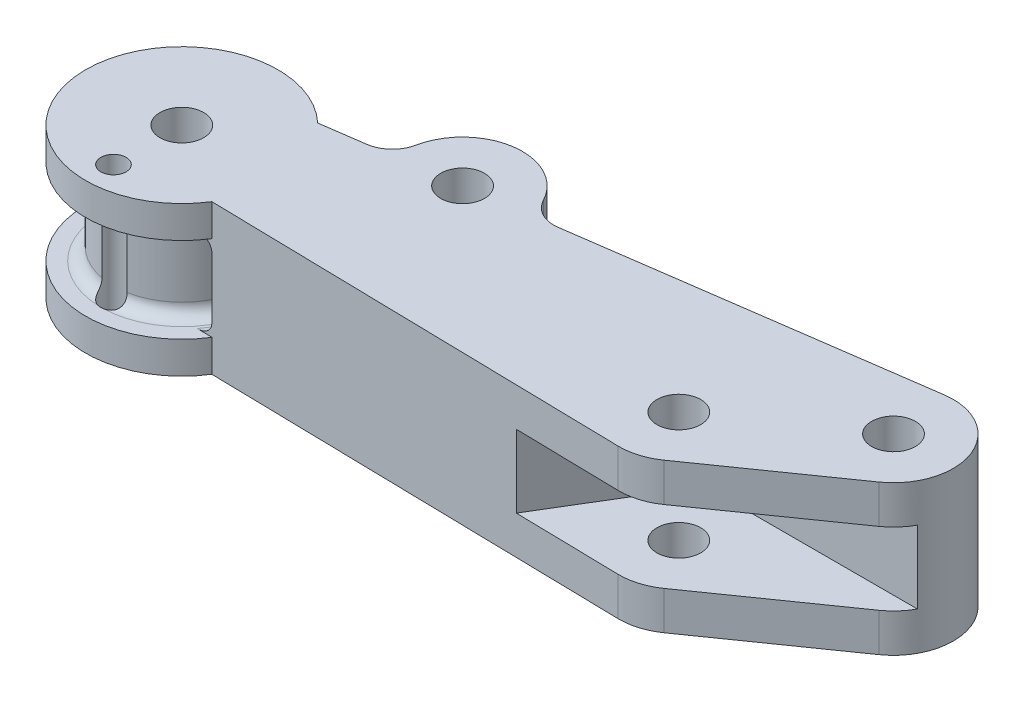
SolidWorks part; units mm, degrees
ref_plane "Front Plane" through (0, 0, 0) normal (0, 0, 1) x (1, 0, 0)
ref_plane "Top Plane" through (0, 0, 0) normal (0, 1, 0) x (1, 0, 0)
ref_plane "Right Plane" through (0, 0, 0) normal (1, 0, 0) x (0, 0, -1)
sketch "Sketch1" plane through (0, 0, 0) normal (0, 1, 0) x (1, 0, 0)
  line L0 (0, 0) -> (29.5515, 0)
  line L1 (4.8343, -3.048) -> (29.4783, -3.5552)
  line L2 (39.0998, 2.3447) -> (31.5912, -2.9129)
  line L3 (29.5515, 0) -> (37.0601, 5.2576)
  line L4 (37.0601, 5.2576) -> (0, 0)
  line L5 (36.5607, 8.7784) -> (16.4608, 5.9268)
  line L6 (6.4883, 4.5121) -> (3.9301, 4.1492)
  line L7 (29.5515, 3.556) -> (40.1826, 3.556)
  line L8 (26.5092, 1.841) -> (23.3205, -3.4285)
  circle A0 centre (37.0601, 5.2576) radius 1.3
  circle A1 centre (29.5515, 0) radius 1.3
  circle A2 centre (0, 0) radius 1.3
  circle A3 centre (0, 0) radius 5.715
  arc A4 (36.5607, 8.7784) -> (39.0998, 2.3447) centre (37.0601, 5.2576) cw
  arc A5 (31.5912, -2.9129) -> (29.4783, -3.5552) centre (29.5515, 0) cw
  circle A6 centre (0, -4.064) radius 0.75
  circle A7 centre (11.4746, 5.2195) radius 1.3
  arc A8 (14.6252, 6.8682) -> (7.9896, 5.9268) centre (11.4746, 5.2195) ccw
  arc A9 (14.6252, 6.8682) -> (16.4608, 5.9268) centre (16.2096, 7.6973) ccw
  arc A10 (7.9896, 5.9268) -> (6.4883, 4.5121) centre (6.2372, 6.2826) cw
  circle A11 centre (0, 0) radius 4.064
  circle A12 centre (11.4746, 5.2195) radius 3.556
  circle A13 centre (29.5515, 0) radius 3.556
  dimension "D2" = 2.6
  dimension "D5" = 11.43
  dimension "D8" = 2.6
  dimension "D11" = 8.128
  dimension "D12" = 1.5
  dimension "D3" = 29.5515
  dimension "D4" = 9.1664
  dimension "D6" = 3.048
  dimension "D7" = 3.556
  dimension "D9" = 7.62
  dimension "D10" = 145
  dimension "D13" = 60
extrude "Boss-Extrude1" add sketch "Sketch1" along normal blind 8.89 contours A12 A8 A7 | L4 A11 L0 A2 | A12 L4 A0 L3 A1 L0 A3 A5 L2 A4 L5 A9 | A12 A10 L6 A3 L4 | A11 L4 A3 L0 | A3 L0 A1 L3 A0 L4 | A11 L0 A3 L4 | L0 A11 L4 A2 | A3 L1 L8 L0 | A13 L2 A4 L7 L3 | A13 L3 L7 | L3 A13 L0 A1 | A13 L0 L8 L1 | A5 A13 L3 A1 L0 | A13 L8 L0 region at (2.9097, 0, -0.2054) region at (2.682, 0, 0.1145) region at (4.9196, 0, -0.3472) region at (4.8895, 0, 0.1616) region at (20.3303, 0, -1.7431) region at (15.0894, 0, 1.6071) region at (7.0788, 0, -2.757) region at (25.8645, 0, -0.4743) region at (25.6, 0, 2.2908) region at (27.5097, 0, -5.4852) region at (8.9598, 0, -2.8497) region at (28.9616, 0, -1.8709) region at (29.9493, 0, 1.2618) region at (32.5559, 0, -3.0835) region at (35.5535, 0, -1.5908)
extrude "Cut-Extrude1" cut sketch "Sketch1<3>" along normal blind 6.985 contours A11 L0 A3 L4 | A11 A6 L4 A3 L0 region at (4.9196, 0, -0.3472) region at (4.8895, 0, 0.1616)
sketch "Sketch1<3>" plane through (0, 0, 0) normal (0, 1, 0) x (1, 0, 0) same geometry as "Sketch1"
extrude "Boss-Extrude2" add sketch "Sketch1<4>" along normal blind 1.905 contours A11 A6 L4 A3 L0 | A11 L0 A3 L4 region at (4.9196, 0, -0.3472) region at (4.8895, 0, 0.1616)
sketch "Sketch1<4>" plane through (0, 0, 0) normal (0, 1, 0) x (1, 0, 0) same geometry as "Sketch1"
fillet "Fillet4" radius 0.7366 4 edges at (5.6704, 6.985, -0.7124) (0, 6.985, -4.064) (0, 1.905, -4.064) (5.6704, 1.905, -0.7124)
extrude "Cut-Extrude2" cut sketch "Sketch1<5>" along normal blind 5.588 contours A12 A8 A7 region at (8.9598, 0, -2.8497)
sketch "Sketch1<5>" plane through (0, 0, 0) normal (0, 1, 0) x (1, 0, 0) same geometry as "Sketch1"
extrude "Boss-Extrude3" add sketch "Sketch1<6>" along normal blind 3.302 contours A12 A8 A7 region at (8.9598, 0, -2.8497)
sketch "Sketch1<6>" plane through (0, 0, 0) normal (0, 1, 0) x (1, 0, 0) same geometry as "Sketch1"
extrude "Cut-Extrude3" cut sketch "Sketch1<7>" along normal blind 6.604 contours A13 L0 L8 L1 | A13 L3 L7 | L3 A13 L0 A1 | A5 A13 L3 A1 L0 | A13 L2 A4 L7 L3 | A13 L8 L0 region at (25.8645, 0, -0.4743) region at (25.6, 0, 2.2908) region at (28.9616, 0, -1.8709) region at (29.9493, 0, 1.2618) region at (32.5559, 0, -3.0835) region at (35.5535, 0, -1.5908)
sketch "Sketch1<7>" plane through (0, 0, 0) normal (0, 1, 0) x (1, 0, 0) same geometry as "Sketch1"
extrude "Boss-Extrude4" add sketch "Sketch1<8>" along normal blind 2.286 contours A13 L3 L7 | L3 A13 L0 A1 | A13 L8 L0 | A13 L0 L8 L1 | A5 A13 L3 A1 L0 | A13 L2 A4 L7 L3 region at (25.8645, 0, -0.4743) region at (25.6, 0, 2.2908) region at (28.9616, 0, -1.8709) region at (29.9493, 0, 1.2618) region at (32.5559, 0, -3.0835) region at (35.5535, 0, -1.5908)
sketch "Sketch1<8>" plane through (0, 0, 0) normal (0, 1, 0) x (1, 0, 0) same geometry as "Sketch1"
